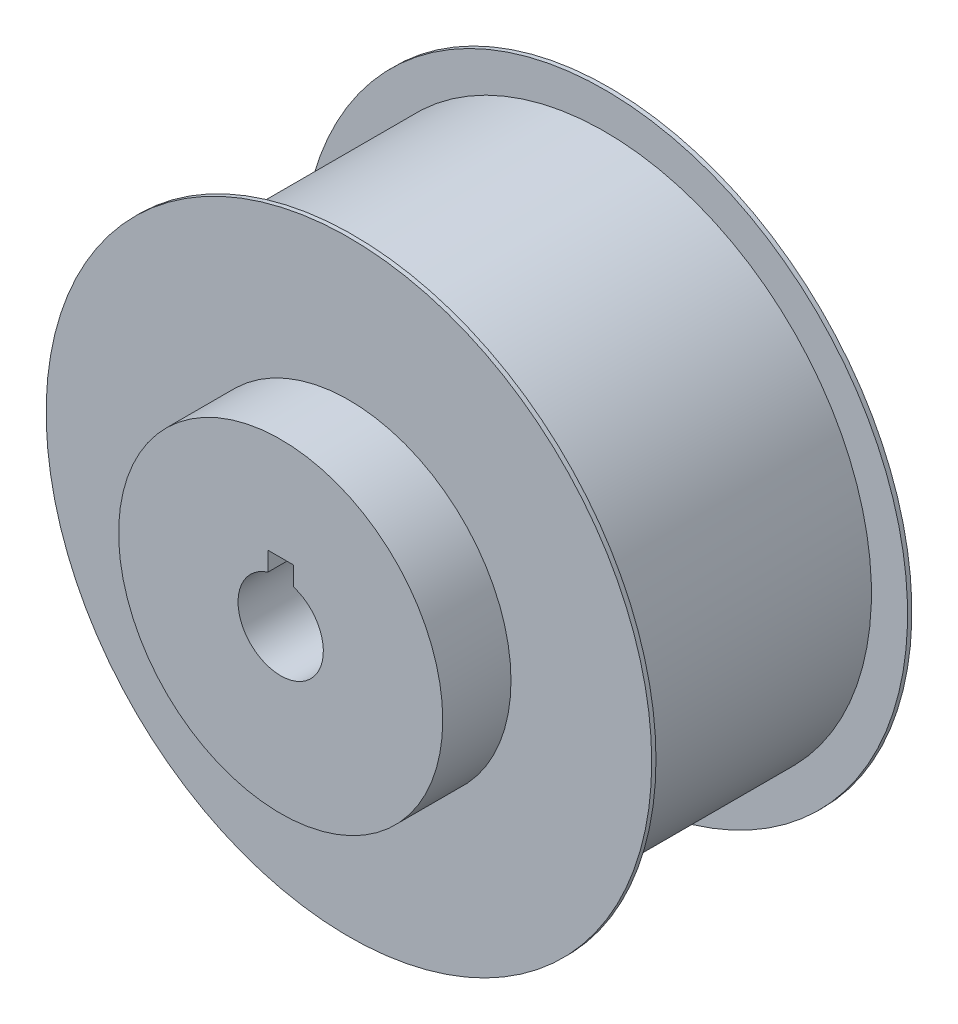
SolidWorks part; units mm, degrees
ref_plane "Płaszczyzna przednia" through (0, 0, 0) normal (0, 0, 1) x (1, 0, 0)
ref_plane "Płaszczyzna górna" through (0, 0, 0) normal (0, 1, 0) x (1, 0, 0)
ref_plane "Płaszczyzna prawa" through (0, 0, 0) normal (1, 0, 0) x (0, 0, -1)
sketch "Szkic1" plane through (0, 0, 0) normal (0, 0, 1) x (1, 0, 0)
  circle A0 centre (0, 0) radius 31.26
  dimension "D1" = 62.52
extrude "Dodanie-wyciągnięcie1" add sketch "Szkic1" along normal blind 30.5
sketch "Szkic2" plane through (0, 0, 30.5) normal (0, 0, 1) x (1, 0, 0)
  circle A0 centre (0, 0) radius 19
  dimension "D1" = 38
extrude "Dodanie-wyciągnięcie2" add sketch "Szkic2" along normal blind 8
sketch "Szkic3" plane through (0, 0, 30.5) normal (0, 0, 1) x (1, 0, 0)
  circle A0 centre (0, 0) radius 35.5
  dimension "D1" = 71
extrude "Dodanie-wyciągnięcie3" add sketch "Szkic3" against normal blind 0.5
sketch "Szkic7" plane through (0, 0, 0) normal (0, 0, -1) x (-1, 0, 0)
  circle A0 centre (0, 0) radius 35.5
  dimension "D1" = 71
extrude "Dodanie-wyciągnięcie4" add sketch "Szkic7" against normal blind 0.5
sketch "Szkic5" plane through (0, 0, 38.5) normal (0, 0, 1) x (1, 0, 0)
  circle A0 centre (0, 0) radius 5
  dimension "D1" = 10
extrude "Wytnij-wyciągnięcie2" cut sketch "Szkic5" against normal through all
sketch "Szkic6" plane through (0, 0, 38.5) normal (0, 0, 1) x (1, 0, 0)
  line L1 (1.5, 0) -> (-1.5, 0)
  line L2 (1.5, 0) -> (1.5, 7)
  line L3 (1.5, 7) -> (-1.5, 7)
  line L4 (-1.5, 0) -> (-1.5, 7)
  line L5 (1.5, 0) -> (-1.5, 7) construction
  line L6 (1.5, 7) -> (-1.5, 0) construction
  point P0 (0, 3.5)
  dimension "D1" = 7
  dimension "D2" = 3
extrude "Wytnij-wyciągnięcie3" cut sketch "Szkic6" against normal blind 40
